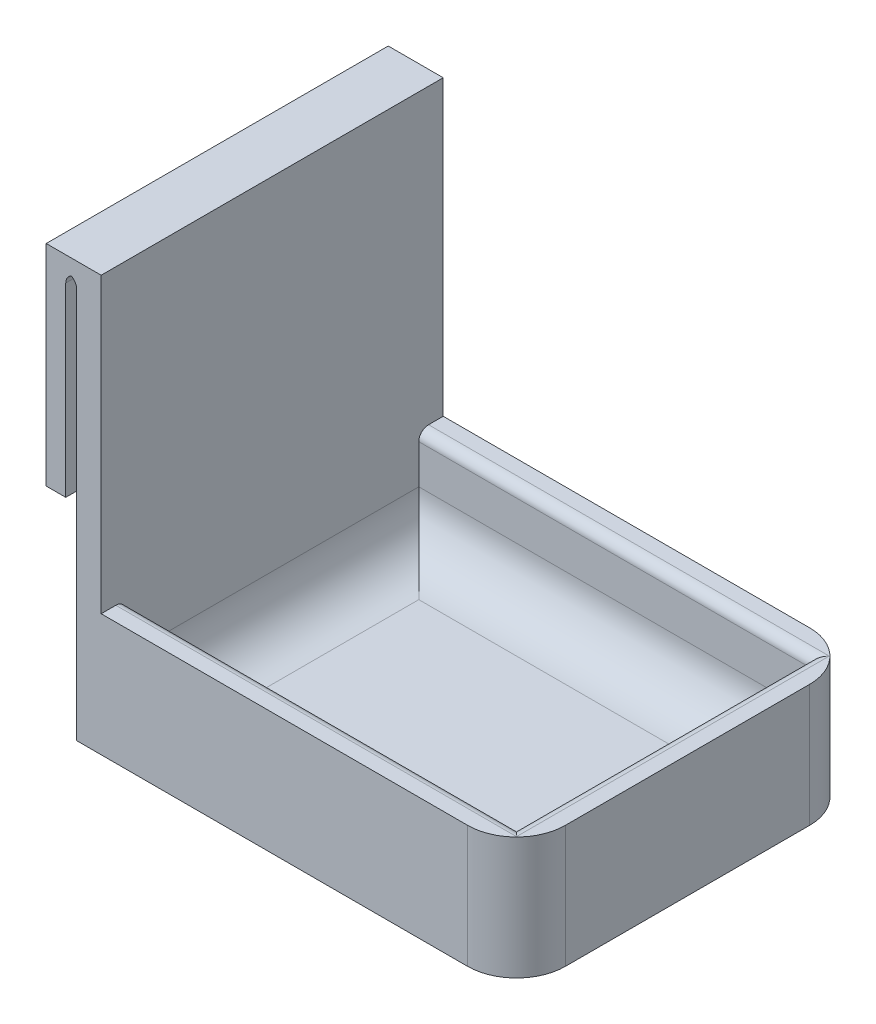
SolidWorks part; units mm, degrees
ref_plane "Front Plane" through (0, 0, 0) normal (0, 0, 1) x (1, 0, 0)
ref_plane "Top Plane" through (0, 0, 0) normal (0, 1, 0) x (1, 0, 0)
ref_plane "Right Plane" through (0, 0, 0) normal (1, 0, 0) x (0, 0, -1)
sketch "Sketch1" plane through (0, 0, 0) normal (0, 1, 0) x (1, 0, 0)
  line L1 (0, 0) -> (90, 0)
  line L2 (0, 0) -> (0, -70)
  line L3 (0, -70) -> (90, -70)
  line L4 (90, 0) -> (90, -70)
  dimension "D1" = 90
  dimension "D2" = 70
extrude "Boss-Extrude1" add sketch "Sketch1" along normal blind 5
sketch "Sketch2" plane through (0, 5, 0) normal (0, 1, 0) x (1, 0, 0)
  line L0 (0, 0) -> (0, -70) construction
  line L1 (5, -5) -> (85, -5)
  line L2 (5, -5) -> (5, -65)
  line L3 (5, -65) -> (85, -65)
  line L4 (85, -5) -> (85, -65)
  line L5 (90, 0) -> (0, 0) construction
  line L6 (90, -70) -> (90, 0) construction
  line L7 (0, -70) -> (90, -70) construction
  line L9 (0, 0) -> (90, 0)
  line L10 (0, 0) -> (0, -70)
  line L11 (0, -70) -> (90, -70)
  line L12 (90, 0) -> (90, -70)
  dimension "D1" = 5
  dimension "D2" = 5
  dimension "D3" = 5
  dimension "D4" = 5
extrude "Boss-Extrude2" add sketch "Sketch2" along normal blind 80
sketch "Sketch3" plane through (0, 0, 0) normal (-1, 0, 0) x (0, 0, 1)
  line L0 (70, 85) -> (70, 0) construction
  line L1 (0, 85) -> (70, 85)
  line L2 (0, 85) -> (0, 82)
  line L3 (0, 82) -> (70, 82)
  line L4 (70, 85) -> (70, 82)
  dimension "D1" = 3
extrude "Boss-Extrude4" add sketch "Sketch3" along normal blind 6.25
sketch "Sketch4" plane through (0, 82, 0) normal (0, -1, 0) x (1, 0, 0)
  line L0 (-6.25, 0) -> (0, 0) construction
  line L1 (-6.25, 70) -> (-2.25, 70)
  line L2 (-6.25, 70) -> (-6.25, 0)
  line L3 (-6.25, 0) -> (-2.25, 0)
  line L4 (-2.25, 70) -> (-2.25, 0)
  dimension "D1" = 4
extrude "Boss-Extrude5" add sketch "Sketch4" along normal blind 40
sketch "Sketch5" plane through (90, 0, 0) normal (1, 0, 0) x (0, 0, -1)
  line L0 (0, 85) -> (0, 0) construction
  line L1 (-70, 85) -> (0, 85)
  line L2 (-70, 85) -> (-70, 25)
  line L3 (-70, 25) -> (0, 25)
  line L4 (0, 85) -> (0, 25)
  dimension "D1" = 60
extrude "Cut-Extrude3" cut sketch "Sketch5" against normal blind 85
fillet "Fillet1" radius 10 4 edges at (45, 5, 5) (85, 5, 35) (5, 5, 35) (45, 5, 65)
fillet "Fillet2" radius 2 2 edges at (0, 82, 35) (-2.25, 82, 35)
fillet "Fillet3" radius 2 3 edges at (45, 25, 65) (85, 25, 35) (45, 25, 5)
fillet "Fillet4" radius 10 2 edges at (90, 12.5, 70) (90, 12.5, 0)
